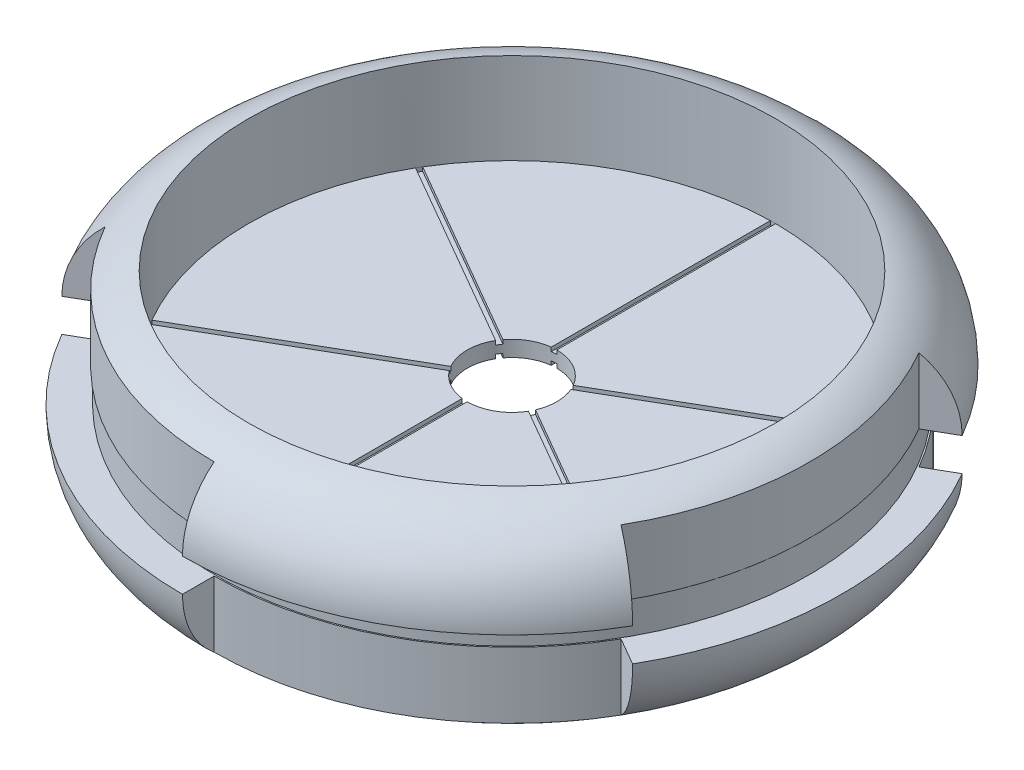
SolidWorks part; units mm, degrees
material "Rubber"
ref_plane "Front" through (0, 0, 0) normal (0, 0, 1) x (1, 0, 0)
ref_plane "Top" through (0, 0, 0) normal (0, 1, 0) x (1, 0, 0)
ref_plane "Right" through (0, 0, 0) normal (1, 0, 0) x (0, 0, -1)
sketch "Sketch1" plane through (0, 0, 0) normal (0, 0, 1) x (1, 0, 0)
  line L0 (-15.875, 4.7625) -> (15.875, 4.7625) construction
  line L1 (0, -4.7625) -> (0, 4.7625) construction
  line L2 (12.7, 0.7937) -> (12.7, -0.7937) construction
  line L3 (-15.875, -4.7625) -> (15.875, -4.7625) construction
  line L4 (-12.7, 0) -> (12.7, 0) construction
  dimension "D1" = 1.5875
  dimension "flange dia" = 31.75
  dimension "oall ht" = 9.525
  dimension "for hole dia" = 25.4
sketch "Sketch2" plane through (0, 0, 0) normal (0, 0, 1) x (1, 0, 0)
  line L0 (15.875, 4.7625) -> (15.875, 0.7937)
  line L1 (15.875, 4.7625) -> (12.7, 4.7625)
  line L2 (-15.875, 4.7625) -> (15.875, 4.7625) construction
  line L3 (15.875, 0.7937) -> (14.2875, 0.7937)
  line L4 (14.2875, 0.7937) -> (14.2875, -0.7937)
  line L5 (14.2875, -0.7937) -> (15.875, -0.7938)
  line L6 (15.875, -0.7938) -> (15.875, -4.7625)
  line L7 (15.875, -4.7625) -> (12.7, -4.7625)
  line L8 (-15.875, -4.7625) -> (15.875, -4.7625) construction
  line L9 (12.7, -4.7625) -> (12.7, 4.7625)
  line L10 (12.7, 0.7937) -> (12.7, -0.7937) construction
  line L11 (-12.7, 0) -> (12.7, 0) construction
  point P8 (14.2875, 0)
  dimension "D1" = 1.5875
revolve "Revolve1" add sketch "Sketch2" angle 360 about L1
sketch "Sketch3" plane through (0, 0, 0) normal (0, 1, 0) x (1, 0, 0)
  circle A0 centre (0, 0) radius 12.7
  circle A1 centre (0, 0) radius 2.159
  dimension "D1" = 4.318
extrude "Boss-Extrude1" add sketch "Sketch3" along normal blind 0.381 and the other way blind 0.381
fillet "Fillet1" radius 4.064 2 edges at (0, -4.7625, -15.875) (0, 4.7625, -15.875)
ref_plane "Plane1" through (0, 4.7625, 0) normal (0, -1, 0) x (1, 0, 0)
sketch "Sketch4" plane through (0, 4.7625, 0) normal (0, -1, 0) x (1, 0, 0)
  line L0 (0, 0) -> (20.1244, 11.6188) construction
  line L1 (20.1244, 11.6188) -> (20.1244, -11.6188) construction
  line L2 (20.1244, -11.6188) -> (0, 0) construction
  line L4 (12.4283, 7.1755) -> (13.7482, 7.9375)
  line L5 (12.4283, -7.1755) -> (13.7482, -7.9375)
  line L6 (-15.875, 0) -> (15.875, 0) construction
  arc A0 (12.4283, 7.1755) -> (12.4283, -7.1755) centre (0, 0) cw
  circle A2 centre (0, 0) radius 15.875 construction
  arc A3 (13.7482, 7.9375) -> (13.7482, -7.9375) centre (0, 0) cw
  circle A4 centre (0, 0) radius 15.875 construction
  circle A5 centre (0, 0) radius 12.7 construction
  point P5 (12.7, 0)
  point P21 (14.351, 0)
  dimension "D1" = 1.651
  dimension "D2" = 20.1244
extrude "Cut-Extrude2" cut sketch "Sketch4" along normal up to surface (3.9688 mm away) up to face at (0, 0.7938, -15.875)
pattern_circular "CirPattern1" count 3 over 360 about axis through (0, 4.7625, 0) along (0, -1, 0) of "Cut-Extrude2"
ref_plane "Plane2" through (0, -4.7625, 0) normal (0, -1, 0) x (1, 0, 0)
sketch "Sketch5" plane through (0, -4.7625, 0) normal (0, -1, 0) x (1, 0, 0)
  line L0 (0, 0) -> (0, 23.2376) construction
  line L1 (0, 23.2376) -> (20.1244, 11.6188) construction
  line L2 (20.1244, 11.6188) -> (0, 0) construction
  line L3 (0, 0) -> (20.1244, 11.6188) construction
  line L4 (0, 15.875) -> (0, 14.351)
  line L5 (13.7482, 7.9375) -> (12.4283, 7.1755)
  line L6 (12.4283, 7.1755) -> (13.7482, 7.9375) construction
  arc A0 (0, 14.351) -> (12.4283, 7.1755) centre (0, 0) cw
  arc A1 (0, 15.875) -> (13.7482, 7.9375) centre (0, 0) cw
  arc A2 (12.4283, -7.1755) -> (12.4283, 7.1755) centre (0, 0) ccw construction
  arc A3 (13.7482, -7.9375) -> (13.7482, 7.9375) centre (0, 0) ccw construction
extrude "Cut-Extrude3" cut sketch "Sketch5" against normal up to vertex (3.9688 mm away) up to point (12.7, -0.7937, 0)
pattern_circular "CirPattern2" count 3 over 360 about axis through (0, -4.7625, 0) along (0, -1, 0) of "Cut-Extrude3"
sketch "Sketch6" plane through (0, 0.381, 0) normal (0, 1, 0) x (1, 0, 0)
  line L0 (0, 0) -> (10.9985, 6.35)
  line L1 (20.1244, 11.6188) -> (0, 0) construction
  line L2 (0, 0) -> (20.1244, -11.6188) construction
  line L3 (10.9985, -6.35) -> (0, 0)
  line L4 (11.1255, -6.13) -> (0.508, 0)
  line L5 (0.508, 0) -> (11.1255, 6.13)
  line L6 (10.9985, -6.35) -> (11.1255, -6.13)
  line L7 (10.9985, 6.35) -> (11.1255, 6.13)
  circle A0 centre (0, 0) radius 12.7 construction
  circle A1 centre (0, 0) radius 12.7 construction
  dimension "D1" = 0.254
extrude "Cut-Extrude4" cut sketch "Sketch6" against normal blind 0.1905
pattern_circular "CirPattern3" count 3 over 360 about axis through (0, 4.7625, 0) along (0, -1, 0) of "Cut-Extrude4"
mirror "Mirror1" about plane through (0, 0, 0) normal (0, 1, 0) of "CirPattern3"
equation "\"D1@Sketch2\"=(\"flange dia@Sketch1\"-\"for hole dia@Sketch1\")/4"
